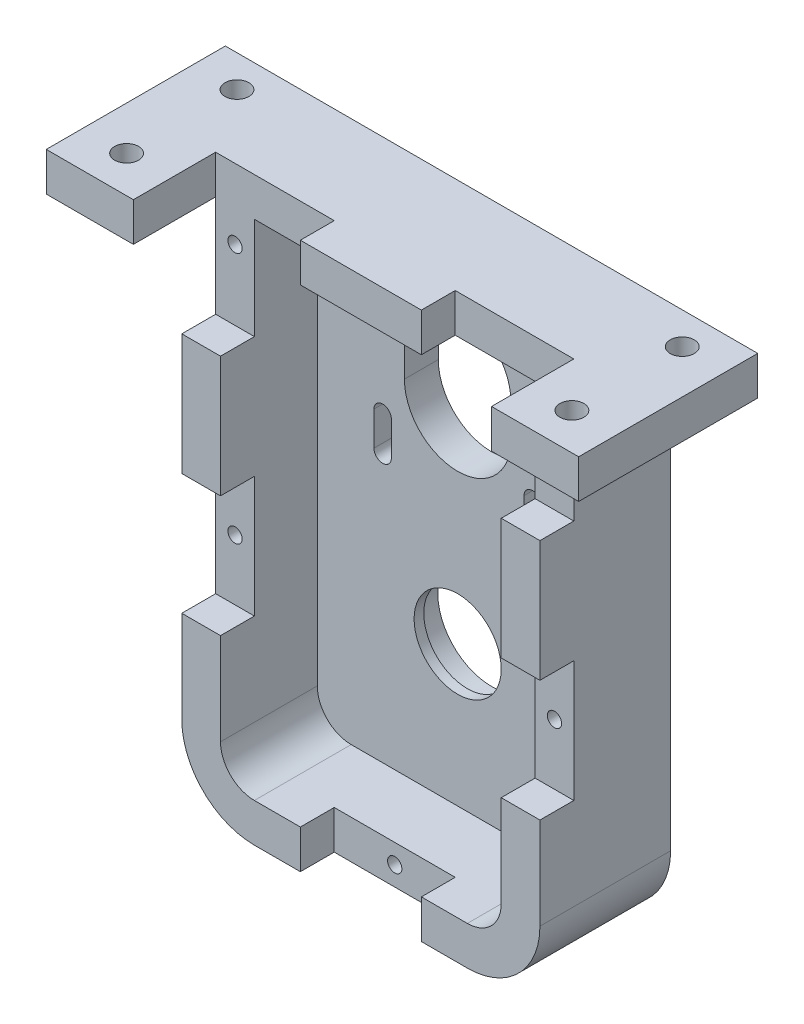
SolidWorks part; units mm, degrees
ref_plane "Alzado" through (0, 0, 0) normal (0, 0, 1) x (1, 0, 0)
ref_plane "Planta" through (0, 0, 0) normal (0, 1, 0) x (1, 0, 0)
ref_plane "Vista lateral" through (0, 0, 0) normal (1, 0, 0) x (0, 0, -1)
sketch "Croquis2" plane through (0, 0, 0) normal (0, 0, 1) x (1, 0, 0)
  line L0 (-30.7866, 48.816) -> (-5.7866, 48.816)
  line L1 (-5.7866, 48.816) -> (-5.7866, 40.816)
  line L2 (-5.7866, 40.816) -> (-30.7866, 40.816)
  line L3 (-30.7866, 48.816) -> (-30.7866, 40.816)
  line L5 (-22.5241, 25.0911) -> (-22.5241, 24.7943)
  line L7 (-18.1703, 25.0911) -> (-18.1703, 24.7943)
  line L8 (-5.7866, 48.816) -> (18.7134, 48.816)
  line L9 (-55.2866, 48.816) -> (-30.7866, 48.816)
  line L10 (18.7134, 48.816) -> (18.7134, 19.816)
  line L11 (-55.2866, 48.816) -> (-55.2866, 19.816)
  line L12 (-55.2866, 19.816) -> (-47.2866, 19.816)
  line L13 (-47.2866, 19.816) -> (-47.2866, 40.816)
  line L14 (-47.2866, 40.816) -> (-30.7866, 40.816)
  line L15 (18.7134, 19.816) -> (10.7134, 19.816)
  line L16 (10.7134, 19.816) -> (10.7134, 40.816)
  line L17 (10.7134, 40.816) -> (-5.7866, 40.816)
  line L18 (-55.2866, 19.816) -> (-55.2866, -5.184)
  line L19 (-55.2866, -5.184) -> (-47.2866, -5.184)
  line L20 (-47.2866, -5.184) -> (-47.2866, 19.816)
  line L21 (10.7134, 19.816) -> (10.7134, -5.184)
  line L22 (18.7134, 19.816) -> (18.7134, -5.184)
  line L23 (10.7134, -5.184) -> (18.7134, -5.184)
  line L24 (-55.2866, -5.184) -> (-55.2866, -30.184)
  line L25 (18.7134, -5.184) -> (18.7134, -30.184)
  line L26 (-47.2866, -5.184) -> (-47.2866, -30.184)
  line L27 (-31.9866, 6.2053) -> (-31.9866, -0.7947)
  line L28 (10.7134, -5.184) -> (10.7134, -30.184)
  line L29 (-55.2866, -30.184) -> (-47.2866, -30.184)
  line L30 (18.7134, -30.184) -> (10.7134, -30.184)
  line L31 (-55.2866, -30.184) -> (-55.2866, -49.184)
  line L32 (18.7134, -30.184) -> (18.7134, -49.184)
  line L34 (-47.2866, -30.184) -> (-47.2866, -49.184)
  line L35 (10.7134, -30.184) -> (10.7134, -49.184)
  line L36 (-47.2866, -49.184) -> (-55.2866, -49.184)
  line L37 (10.7134, -49.184) -> (18.7134, -49.184)
  line L38 (-40.2866, -56.184) -> (-30.7866, -56.184)
  line L39 (3.7134, -56.184) -> (3.7134, -64.184)
  line L40 (-30.7866, -56.184) -> (-30.7866, -64.184)
  line L42 (-30.7866, -64.184) -> (-40.2866, -64.184)
  line L43 (-30.7866, -56.184) -> (-5.7866, -56.184)
  line L44 (-40.2866, -64.184) -> (-40.2866, -56.184)
  line L45 (-5.7866, -56.184) -> (-5.7866, -64.184)
  line L46 (-5.7866, -64.184) -> (-30.7866, -64.184)
  line L47 (3.7134, -64.184) -> (-5.7866, -64.184)
  line L48 (-5.7866, -56.184) -> (3.7134, -56.184)
  line L49 (-4.5866, 30.2053) -> (-4.5866, 37.2053)
  line L50 (-7.2866, 21.7053) -> (-7.2866, 14.7053)
  line L51 (-0.9866, 30.2053) -> (-0.9866, 37.2053)
  line L52 (-29.2866, 21.7053) -> (-29.2866, 14.7053)
  line L53 (-0.9866, 6.2053) -> (-0.9866, -0.7947)
  line L54 (-4.5866, 6.2053) -> (-4.5866, -0.7947)
  line L55 (-35.5866, 6.2053) -> (-35.5866, -0.7947)
  line L56 (-35.5866, 30.2053) -> (-35.5866, 37.2053)
  line L57 (-31.9866, 30.2053) -> (-31.9866, 37.2053)
  line L58 (18.7134, 48.816) -> (36.7134, 48.816)
  line L59 (-55.2866, 48.816) -> (-73.2866, 48.816)
  line L60 (36.7134, 48.816) -> (36.7134, 40.816)
  line L61 (-73.2866, 48.816) -> (-73.2866, 40.816)
  line L62 (36.7134, 40.816) -> (18.7134, 40.816)
  line L63 (-73.2866, 40.816) -> (-55.2866, 40.816)
  arc A0 (-55.2866, -49.184) -> (-40.2866, -64.184) centre (-40.2866, -49.184) ccw
  arc A1 (18.7134, -49.184) -> (3.7134, -64.184) centre (3.7134, -49.184) cw
  arc A2 (-47.2866, -49.184) -> (-40.2866, -56.184) centre (-40.2866, -49.184) ccw
  arc A3 (3.7134, -56.184) -> (10.7134, -49.184) centre (3.7134, -49.184) ccw
  circle A4 centre (-18.2866, -27.184) radius 9
  arc A5 (-7.2866, 21.7053) -> (-29.2866, 21.7053) centre (-18.2866, 21.7053) ccw
  arc A7 (-29.2866, 14.7053) -> (-7.2866, 14.7053) centre (-18.2866, 14.7053) ccw
  arc A8 (-0.9866, 37.2053) -> (-4.5866, 37.2053) centre (-2.7866, 37.2053) ccw
  arc A9 (-4.5866, 30.2053) -> (-0.9866, 30.2053) centre (-2.7866, 30.2053) ccw
  arc A10 (-4.5866, 6.2053) -> (-0.9866, 6.2053) centre (-2.7866, 6.2053) cw
  arc A11 (-0.9866, -0.7947) -> (-4.5866, -0.7947) centre (-2.7866, -0.7947) cw
  arc A12 (-35.5866, -0.7947) -> (-31.9866, -0.7947) centre (-33.7866, -0.7947) ccw
  arc A13 (-31.9866, 6.2053) -> (-35.5866, 6.2053) centre (-33.7866, 6.2053) ccw
  arc A14 (-31.9866, 30.2053) -> (-35.5866, 30.2053) centre (-33.7866, 30.2053) cw
  arc A15 (-35.5866, 37.2053) -> (-31.9866, 37.2053) centre (-33.7866, 37.2053) cw
extrude "Saliente-Extruir1" add sketch "Croquis2" along normal blind 7 contours L48 A3 L35 L28 L21 L16 L17 L2 L14 L13 L20 L26 L34 A2 L38 L43 A13 L27 A12 L55 A9 L49 A8 L51 A7 L52 A5 L50 A4 L53 A11 L54 A10 L56 A15 L57 A14 region at (-18.2866, -10.1531, 0)
extrude "Saliente-Extruir2" add sketch "Croquis2<5>" along normal blind 37 separate body contours L62 L60 L58 L10 | L61 L63 L11 L59 region at (-64.2866, 44.816, 0) region at (27.7134, 44.816, 0)
sketch "Croquis2<5>" plane through (0, 0, 0) normal (0, 0, 1) x (1, 0, 0) same geometry as "Croquis2"
extrude "Saliente-Extruir3" add sketch "Croquis2<7>" along normal blind 27 contours L0 L3 L2 L1 | L19 L20 L12 L18 | L36 L34 L29 L31 | A2 L36 A0 L44 | L44 L42 L40 L38 | L48 L45 L47 L39 | A3 L39 A1 L37 | L35 L37 L32 L30 | L21 L23 L22 L15 region at (-18.2866, 44.816, 0) region at (-51.2866, 7.316, 0) region at (14.7134, 7.316, 0) region at (-51.2866, -39.684, 0) region at (14.7134, -39.684, 0) region at (-47.5981, -56.4955, 0) region at (11.0249, -56.4955, 0) region at (-35.5366, -60.184, 0) region at (-1.0366, -60.184, 0)
sketch "Croquis2<7>" plane through (0, 0, 0) normal (0, 0, 1) x (1, 0, 0) same geometry as "Croquis2"
extrude "Saliente-Extruir4" add sketch "Croquis2<8>" along normal blind 20 contours L13 L14 L3 L9 L11 L12 | L24 L29 L26 L19 | L46 L45 L43 L40 | L30 L25 L23 L28 | L17 L16 L15 L10 L8 L1 region at (-31.1663, 44.816, 0) region at (6.4634, 48.4364, 0) region at (-51.2866, -17.684, 0) region at (14.7134, -17.684, 0) region at (-18.2866, -60.184, 0)
sketch "Croquis2<8>" plane through (0, 0, 0) normal (0, 0, 1) x (1, 0, 0) same geometry as "Croquis2"
sketch "Croquis3" plane through (0, 0, 0) normal (0, 0, -1) x (-1, 0, 0)
  circle A0 centre (18.2866, -27.184) radius 11.1
extrude "Cortar-Extruir1" cut sketch "Croquis3" against normal blind 5
sketch "Croquis9" plane through (0, 40.816, 0) normal (0, -1, 0) x (1, 0, 0)
  line L0 (-69.8266, 29.4) -> (-67.0566, 24.6022)
  line L4 (33.2534, 6.6) -> (30.4834, 11.3978)
  line L5 (30.4834, 11.3978) -> (24.9434, 11.3978)
  line L6 (24.9434, 11.3978) -> (22.1734, 6.6)
  line L7 (22.1734, 6.6) -> (24.9434, 1.8022)
  line L8 (24.9434, 1.8022) -> (30.4834, 1.8022)
  line L9 (30.4834, 1.8022) -> (33.2534, 6.6)
  line L11 (30.4834, 34.1978) -> (33.2534, 29.4)
  line L12 (24.9434, 34.1978) -> (30.4834, 34.1978)
  line L13 (22.1734, 29.4) -> (24.9434, 34.1978)
  line L14 (24.9434, 24.6022) -> (22.1734, 29.4)
  line L15 (30.4834, 24.6022) -> (24.9434, 24.6022)
  line L16 (33.2534, 29.4) -> (30.4834, 24.6022)
  line L17 (-67.0566, 24.6022) -> (-61.5166, 24.6022)
  line L18 (-61.5166, 24.6022) -> (-58.7466, 29.4)
  line L19 (-58.7466, 29.4) -> (-61.5166, 34.1978)
  line L20 (-61.5166, 34.1978) -> (-67.0566, 34.1978)
  line L21 (-67.0566, 34.1978) -> (-69.8266, 29.4)
  line L22 (-67.0566, 1.8022) -> (-69.8266, 6.6)
  line L23 (-61.5166, 1.8022) -> (-67.0566, 1.8022)
  line L24 (-58.7466, 6.6) -> (-61.5166, 1.8022)
  line L25 (-61.5166, 11.3978) -> (-58.7466, 6.6)
  line L26 (-67.0566, 11.3978) -> (-61.5166, 11.3978)
  line L27 (-69.8266, 6.6) -> (-67.0566, 11.3978)
  circle A0 centre (27.7134, 6.6) radius 2.475
  circle A2 centre (27.7134, 29.4) radius 2.475
  circle A3 centre (-64.2866, 29.4) radius 2.475
  circle A4 centre (-64.2866, 6.6) radius 2.475
sketch "Croquis10" plane through (0, 40.816, 0) normal (0, -1, 0) x (1, 0, 0)
  circle A0 centre (-64.2866, 29.4) radius 2.475
  circle A1 centre (-64.2866, 6.6) radius 2.475
  circle A2 centre (27.7134, 29.4) radius 2.475
  circle A3 centre (27.7134, 6.6) radius 2.475
extrude "Cortar-Extruir2" cut sketch "Croquis9" against normal blind 2.5
extrude "Cortar-Extruir3" cut sketch "Croquis10" against normal blind 8
sketch "Croquis11" plane through (0, 0, 20) normal (0, 0, 1) x (1, 0, 0)
  circle A0 centre (-51.2866, 34.316) radius 1.475
  circle A1 centre (-51.2866, -17.684) radius 1.475
  circle A2 centre (-18.2866, -60.184) radius 1.475
  circle A3 centre (14.7134, -17.684) radius 1.475
  circle A4 centre (14.7134, 34.316) radius 1.475
extrude "Cortar-Extruir4" cut sketch "Croquis11" against normal blind 7
